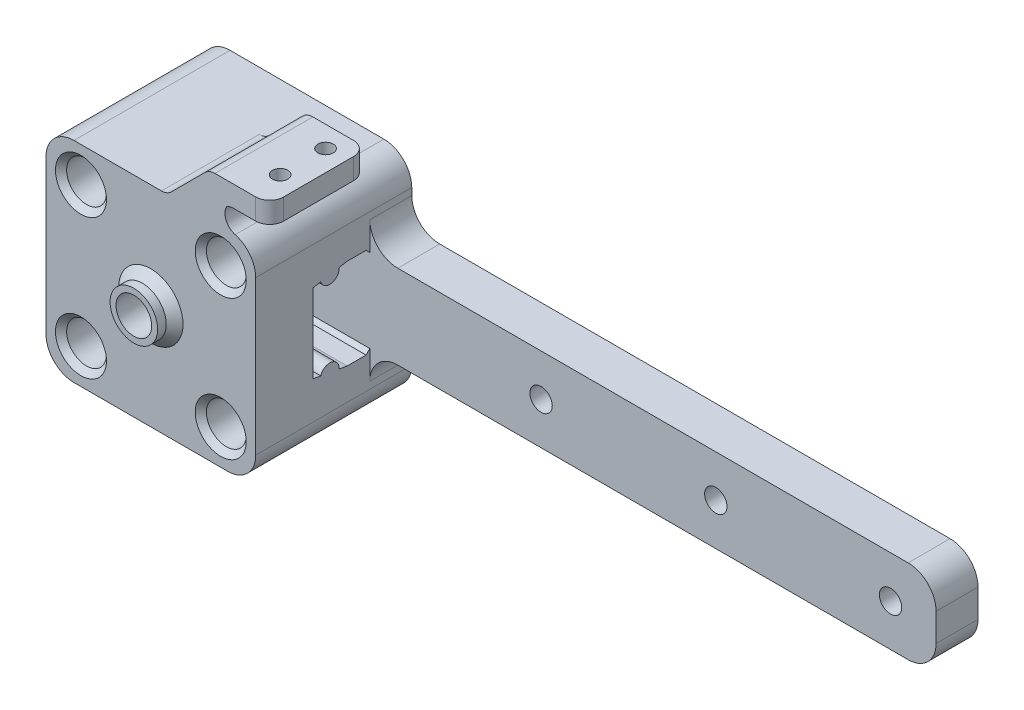
SolidWorks part; units mm, degrees
ref_plane "Front Plane" through (0, 0, 0) normal (0, 0, 1) x (1, 0, 0)
ref_plane "Top Plane" through (0, 0, 0) normal (0, 1, 0) x (1, 0, 0)
ref_plane "Right Plane" through (0, 0, 0) normal (1, 0, 0) x (0, 0, -1)
sketch "Sketch1" plane through (0, 0, 0) normal (0, 0, 1) x (1, 0, 0)
  line L0 (10, 20) -> (10, 0) construction
  line L1 (0, 0) -> (20, 0) construction
  line L2 (0, 0) -> (0, 20) construction
  line L3 (0, 20) -> (20, 20) construction
  line L4 (20, 0) -> (20, 20) construction
  line L5 (10, 10) -> (68.0208, 10) construction
  line L6 (-5, -5) -> (25, -5)
  line L7 (-5, -5) -> (-5, 25)
  line L8 (-5, 25) -> (25, 25)
  line L9 (25, -5) -> (25, 25)
  line L10 (-5, -5) -> (25, 25) construction
  line L11 (-5, 25) -> (25, -5) construction
  line L13 (25, 16) -> (106.01, 16)
  line L14 (25, 16) -> (25, 4)
  line L15 (25, 4) -> (106.01, 4)
  line L16 (106.01, 16) -> (106.01, 4)
  circle A0 centre (0, 0) radius 1.6
  circle A1 centre (0, 20) radius 1.6
  circle A2 centre (20, 20) radius 1.6
  circle A3 centre (20, 0) radius 1.6
  point P11 (10, 10)
  dimension "D2" = 3.2
  dimension "D1" = 20
  dimension "D3" = 30
  dimension "D4" = 30
  dimension "D5" = 12
  dimension "D6" = 6
  dimension "D7" = 81.01
extrude "Boss-Extrude1" add sketch "Sketch1" along normal blind 6 contours L6 L9 L8 L7 A3 A2 A1 A0 | L16 L13 L9 L15 region at (10, 10, 0) region at (65.505, 10, 0)
extrude "Boss-Extrude2" add sketch "Sketch1<3>" along normal blind 22.33 contours L6 L9 L8 L7 A3 A2 A1 A0 region at (10, 10, 0)
sketch "Sketch1<3>" plane through (0, 0, 0) normal (0, 0, 1) x (1, 0, 0) same geometry as "Sketch1"
sketch "Sketch2" plane through (25, 0, 0) normal (1, 0, 0) x (0, 0, -1)
  line L0 (-6.5408, 16.4886) -> (-9.2445, 16.4886)
  line L1 (-9.2445, 16.4886) -> (-10.3819, 16.2881)
  line L2 (-13.0245, 15.8221) -> (-14.1113, 15.6305)
  line L3 (-14.1113, 15.6305) -> (-14.1113, 4.3688)
  line L4 (-14.1113, 4.3688) -> (-13.0245, 4.1771)
  line L5 (-10.3819, 3.7112) -> (-9.2445, 3.5106)
  line L6 (-9.2445, 3.5106) -> (-6.5408, 3.5106)
  line L7 (-6.5408, 3.5106) -> (-6, 4.0514)
  line L9 (-6, 15.9479) -> (-6.5408, 16.4886)
  line L11 (-22.33, -5) -> (0, -5) construction
  line L12 (-22.33, -5) -> (-22.33, 25) construction
  line L13 (-6, 15.9479) -> (-6, 4.0514)
  arc A0 (-13.0245, 15.8221) -> (-10.3819, 16.2881) centre (-11.732, 16.2183) ccw
  arc A1 (-10.3819, 3.7112) -> (-13.0245, 4.1771) centre (-11.732, 3.781) ccw
extrude "Cut-Extrude1" cut sketch "Sketch2" against normal through all
sketch "Sketch3" plane through (0, 0, 22.33) normal (0, 0, 1) x (1, 0, 0)
  line L0 (-5, 10) -> (25, 10) construction
  line L1 (-5, -5) -> (-5, 25) construction
  line L2 (25, -5) -> (25, 25) construction
  line L3 (10, -5) -> (10, 25) construction
  line L4 (-5, -5) -> (25, -5) construction
  line L5 (-5, 25) -> (25, 25) construction
  circle A0 centre (10, 10) radius 2.55
  dimension "D1" = 5.1
extrude "Cut-Extrude2" cut sketch "Sketch3" against normal blind 8
sketch "Sketch5" plane through (0, 0, 14.1113) normal (0, 0, -1) x (-1, 0, 0)
  line L1 (-5.3235, 10) -> (-7.6617, 14.05)
  line L2 (-7.6617, 14.05) -> (-12.3383, 14.05)
  line L3 (-12.3383, 14.05) -> (-14.6765, 10)
  line L4 (-14.6765, 10) -> (-12.3383, 5.95)
  line L5 (-12.3383, 5.95) -> (-7.6617, 5.95)
  line L6 (-7.6617, 5.95) -> (-5.3235, 10)
  line L8 (-25, 15.6305) -> (-25, 4.3688)
  line L9 (-25, 4.3688) -> (5, 4.3688)
  line L10 (5, 4.3688) -> (5, 15.6305)
  line L11 (5, 15.6305) -> (-25, 15.6305)
  line L12 (-25, 15.6305) -> (-25, 4.3688)
  line L13 (-25, 4.3688) -> (5, 4.3688)
  line L15 (5, 15.6305) -> (-25, 15.6305)
  line L18 (5, 4.3688) -> (5, 15.6305)
  circle A0 centre (-10, 10) radius 4.05
  circle A1 centre (-10, 10) radius 4.05 construction
  dimension "D2" = 8.1
  dimension "D3" = 8.1
  dimension "D1" = 0
extrude "Cut-Extrude3" cut sketch "Sketch5" against normal blind 4.5 contours A0 | A0 L2 L3 | A0 L3 L4 | A0 L4 L5 | A0 L5 L6 | A0 L6 L1 | A0 L1 L2 region at (5.8141, 10, 14.1113) region at (7.907, 13.6251, 14.1113) region at (10, 10, 14.1113) region at (7.907, 6.3749, 14.1113) region at (12.093, 13.6251, 14.1113) region at (12.093, 6.3749, 14.1113) region at (14.1859, 10, 14.1113)
sketch "Sketch6" plane through (0, 0, 0) normal (0, 0, -1) x (-1, 0, 0)
  line L0 (-20, 0) -> (0, 20) construction
  line L1 (0, 20) -> (0, 0) construction
  line L2 (0, 0) -> (-20, 20) construction
  circle A0 centre (-10, 10) radius 5
  dimension "D1" = 10
extrude "Cut-Extrude5" cut sketch "Sketch6" against normal blind 8.6
sketch "Sketch7" plane through (0, 0, 0) normal (0, 0, -1) x (-1, 0, 0)
  line L1 (5, -5) -> (-3.5, -5)
  line L2 (5, -5) -> (5, 25)
  line L3 (5, 25) -> (-3.5, 25)
  line L4 (-3.5, -5) -> (-3.5, 25)
  line L5 (5, 25) -> (-25, 25) construction
  line L6 (-106.01, 10) -> (-3.5, 10) construction
  line L7 (-106.01, 16) -> (-106.01, 4) construction
  line L8 (-3.5, 10) -> (-3.5, 16)
  line L9 (-25, 4) -> (-106.01, 4) construction
  line L10 (-3.5, 16) -> (-65, 16)
  line L11 (-3.5, 16) -> (-3.5, 4)
  line L12 (-3.5, 4) -> (-65, 4)
  line L13 (-65, 16) -> (-65, 4)
  circle A0 centre (-49.5, 10) radius 1.6
  circle A1 centre (-74.5, 10) radius 1.6
  circle A2 centre (-99.5, 10) radius 1.6
  dimension "D4" = 46
  dimension "D5" = 25
  dimension "D6" = 3.2
  dimension "D7" = 3.2
  dimension "D1" = 30
  dimension "D2" = 8.5
  dimension "D3" = 6
  dimension "D8" = 25
extrude "Cut-Extrude6" cut sketch "Sketch7" against normal through all contours L6 A2 | A2 L6 | A1 | A0 region at (99.5, 9.3209, 0) region at (99.5, 10.6791, 0)
sketch "Sketch8" plane through (0, 0, 22.33) normal (0, 0, 1) x (1, 0, 0)
  circle A0 centre (20, 20) radius 2.85
  circle A1 centre (20, 0) radius 2.85
  circle A2 centre (0, 0) radius 2.85
  circle A3 centre (0, 20) radius 2.85
  dimension "D4" = 5.7
extrude "Cut-Extrude7" cut sketch "Sketch8" against normal blind 18
sketch "Sketch9" plane through (0, 0, 22.33) normal (0, 0, 1) x (1, 0, 0)
  circle A0 centre (10, 10) radius 2.55
  circle A1 centre (10, 10) radius 3.4
  dimension "D1" = 5.1
  dimension "D2" = 6.8
extrude "Boss-Extrude3" add sketch "Sketch9" along normal blind 2.43
chamfer "Chamfer1" distance 1.2 angle 45 1 edges at (13.4, 10, 22.33)
fillet "Fillet3" radius 4 8 edges at (25, 4, 3) (25, 16, 3) (25, 25, 11.165) (-5, 25, 11.165) (-5, -5, 11.165) (25, -5, 11.165) (106.01, 4, 3) (106.01, 16, 3)
chamfer "Chamfer2" distance 0.8 angle 45 4 edges at (22.85, 0, 22.33) (2.85, 0, 22.33) (2.85, 20, 22.33) (22.85, 20, 22.33)
sketch "Sketch10" plane through (0, 0, 0) normal (0, 0, -1) x (-1, 0, 0)
  line L1 (-97.8834, 12.8) -> (-101.1166, 12.8)
  line L2 (-101.1166, 12.8) -> (-102.7332, 10)
  line L3 (-102.7332, 10) -> (-101.1166, 7.2)
  line L4 (-101.1166, 7.2) -> (-97.8834, 7.2)
  line L5 (-97.8834, 7.2) -> (-96.2668, 10)
  line L6 (-96.2668, 10) -> (-97.8834, 12.8)
  circle A3 centre (-99.5, 10) radius 2.8 construction
  dimension "D1" = 5.6
sketch "Sketch15" plane through (0, 0, 22.33) normal (0, 0, 1) x (1, 0, 0)
  line L0 (12.3431, 25) -> (18.3431, 31)
  line L1 (18.3431, 31) -> (27, 31)
  line L2 (27, 31) -> (27, 28)
  line L3 (27, 28) -> (21, 28)
  line L4 (25, -1) -> (25, 21)
  line L5 (21, 25) -> (-1, 25)
  line L6 (-5, 21) -> (-5, -1)
  line L7 (-1, -5) -> (21, -5)
  line L8 (25, -1) -> (25, 21)
  line L9 (21, 25) -> (-1, 25)
  line L10 (-5, 21) -> (-5, -1)
  line L11 (-1, -5) -> (21, -5)
  line L12 (21, 28) -> (18, 25)
  arc A4 (25, 21) -> (21, 25) centre (21, 21) ccw
  arc A5 (-1, 25) -> (-5, 21) centre (-1, 21) ccw
  arc A6 (-5, -1) -> (-1, -5) centre (-1, -1) ccw
  arc A7 (21, -5) -> (25, -1) centre (21, -1) ccw
  arc A8 (25, 21) -> (21, 25) centre (21, 21) ccw
  arc A9 (-1, 25) -> (-5, 21) centre (-1, 21) ccw
  arc A10 (-5, -1) -> (-1, -5) centre (-1, -1) ccw
  arc A11 (21, -5) -> (25, -1) centre (21, -1) ccw
  dimension "D2" = 3
  dimension "D3" = 3
  dimension "D4" = 4
  dimension "D5" = 3
  dimension "D6" = 45
  dimension "D7" = 6
  dimension "D1" = 0
extrude "Boss-Extrude6" add sketch "Sketch15" against normal blind 14 contours L12 L3 L2 L1 L0 L9 region at (20.0198, 28.3794, 22.33)
sketch "Sketch17" plane through (0, 31, 0) normal (0, 1, 0) x (1, 0, 0)
  line L0 (27, -8.33) -> (27, -22.33) construction
  line L1 (18.3431, -8.33) -> (27, -8.33) construction
  circle A0 centre (24, -11.33) radius 1.1
  circle A1 centre (24, -17.83) radius 1.1
  dimension "D1" = 2.2
  dimension "D2" = 6.5
  dimension "D3" = 3
  dimension "D4" = 3
  dimension "D5" = 3
extrude "Cut-Extrude10" cut sketch "Sketch17" against normal up to next
fillet "Fillet5" radius 2 6 edges at (21, 28, 15.33) (27, 29.5, 22.33) (27, 29.5, 8.33) (18.3431, 31, 15.33) (12.3431, 25, 15.33) (18, 25, 15.33)
extrude "Cut-Extrude11" cut sketch "Sketch10" against normal blind 3
chamfer "Chamfer3" distance 0.8 angle 45 6 edges at (101.9249, 8.6, 0) (99.5, 7.2, 0) (97.0751, 8.6, 0) (101.9249, 11.4, 0) (97.0751, 11.4, 0) (99.5, 12.8, 0)
pattern_linear "LPattern2" count 3 spacing 25 along (-1, 0, 0) of "Chamfer3", "Cut-Extrude11"
